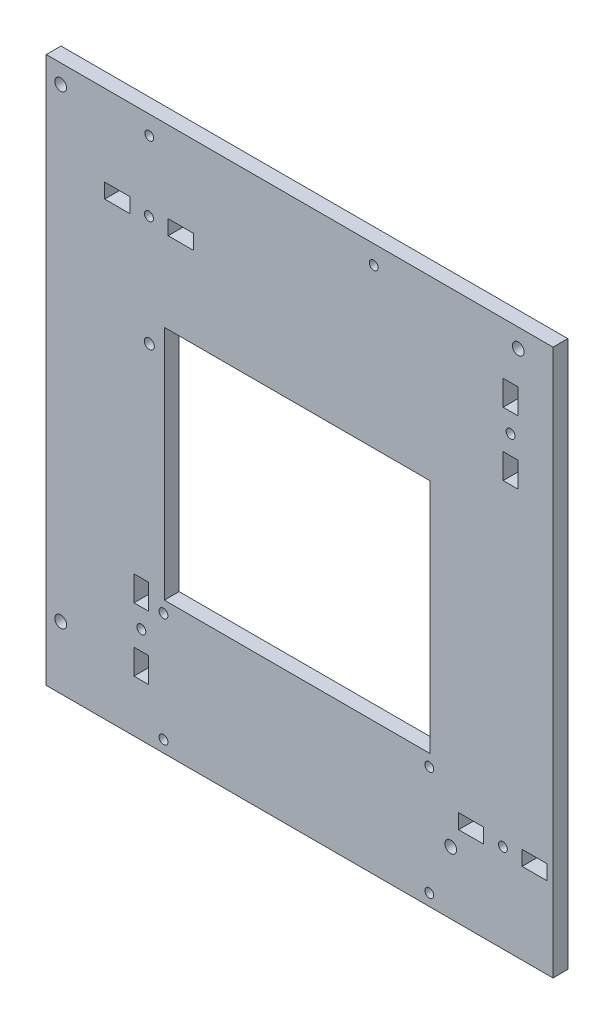
SolidWorks part; units mm, degrees
ref_plane "Front Plane" through (0, 0, 0) normal (0, 0, 1) x (1, 0, 0)
ref_plane "Top Plane" through (0, 0, 0) normal (0, 1, 0) x (1, 0, 0)
ref_plane "Right Plane" through (0, 0, 0) normal (1, 0, 0) x (0, 0, -1)
sketch "Sketch2" plane through (0, 0, 0) normal (0, 0, 1) x (1, 0, 0)
  line L0 (104.43, 85) -> (-85, -100) construction
  line L1 (-85, 85) -> (104.43, 85)
  line L2 (-85, 85) -> (-85, -100)
  line L3 (-85, -100) -> (104.43, -100)
  line L4 (104.43, 85) -> (104.43, -100)
  line L5 (96.43, 71.875) -> (96.43, 85) construction
  line L6 (88.43, -89.415) -> (87.11, -89.415) construction
  line L7 (96.43, -86.875) -> (96.43, -100) construction
  line L8 (88.43, 73.415) -> (88.43, -88.415) construction
  line L9 (87.11, -89.415) -> (87.11, 73.415) construction
  line L10 (88.43, 74.415) -> (87.11, 74.415) construction
  line L11 (-80.1, 78.65) -> (51.98, 78.65) construction
  line L12 (-80.1, 78.65) -> (-80.1, -78.83) construction
  line L13 (-80.1, -78.83) -> (51.98, -78.83) construction
  line L14 (51.98, 78.65) -> (51.98, -78.83) construction
  line L15 (74.84, 78.65) -> (-80.1, 78.65) construction
  line L16 (74.84, 78.65) -> (74.84, -78.83) construction
  line L17 (74.84, -78.83) -> (-80.1, -78.83) construction
  line L18 (-80.1, 78.65) -> (-80.1, -78.83) construction
  line L19 (88.93, -89.915) -> (86.61, -89.915)
  line L20 (88.93, -89.915) -> (88.93, 74.915)
  line L21 (88.93, 74.915) -> (86.61, 74.915)
  line L22 (86.61, -89.915) -> (86.61, 74.915)
  line L23 (88.93, -89.915) -> (86.61, 74.915) construction
  line L24 (88.93, 74.915) -> (86.61, -89.915) construction
  line L25 (-56.7109, 57.5) -> (-65.2109, 57.5)
  line L26 (25.9, 78.65) -> (-50.1, 78.65) construction
  line L27 (45, -55) -> (-45, -55)
  line L28 (45, -55) -> (45, 25)
  line L29 (45, 25) -> (-45, 25)
  line L30 (-45, -55) -> (-45, 25)
  line L31 (45, -55) -> (-45, 25) construction
  line L32 (45, 25) -> (-45, -55) construction
  line L33 (25.9, 78.65) -> (25.9, 17.65) construction
  line L34 (25.9, 17.65) -> (-50.1, 17.65) construction
  line L35 (-50.1, 78.65) -> (-50.1, 17.65) construction
  line L36 (-35.2109, 52.5) -> (-43.7109, 52.5)
  line L37 (-35.2109, 52.5) -> (-35.2109, 57.5)
  line L38 (-35.2109, 57.5) -> (-43.7109, 57.5)
  line L39 (-65.2109, 52.5) -> (-65.2109, 57.5)
  line L40 (-43.7109, 55) -> (-56.7109, 55) construction
  line L41 (-43.7109, 52.5) -> (-43.7109, 57.5)
  line L42 (74.715, 58.9259) -> (74.715, 67.4259)
  line L43 (-56.7109, 52.5) -> (-56.7109, 57.5)
  line L44 (-56.7109, 52.5) -> (-65.2109, 52.5)
  line L45 (69.715, 37.4259) -> (69.715, 45.9259)
  line L46 (69.715, 37.4259) -> (74.715, 37.4259)
  line L47 (74.715, 37.4259) -> (74.715, 45.9259)
  line L48 (69.715, 67.4259) -> (74.715, 67.4259)
  line L49 (69.715, 45.9259) -> (74.715, 45.9259)
  line L50 (69.715, 58.9259) -> (74.715, 58.9259)
  line L51 (69.715, 58.9259) -> (69.715, 67.4259)
  line L52 (72.215, 45.9259) -> (72.215, 58.9259) construction
  line L53 (76.1409, -72.5) -> (84.6409, -72.5)
  line L54 (54.6409, -67.5) -> (63.1409, -67.5)
  line L55 (54.6409, -67.5) -> (54.6409, -72.5)
  line L56 (54.6409, -72.5) -> (63.1409, -72.5)
  line L57 (84.6409, -67.5) -> (84.6409, -72.5)
  line L58 (63.1409, -67.5) -> (63.1409, -72.5)
  line L59 (76.1409, -67.5) -> (76.1409, -72.5)
  line L60 (76.1409, -67.5) -> (84.6409, -67.5)
  line L61 (63.1409, -70) -> (76.1409, -70) construction
  line L62 (-55.285, -73.9259) -> (-55.285, -82.4259)
  line L63 (-50.285, -52.4259) -> (-50.285, -60.9259)
  line L64 (-50.285, -52.4259) -> (-55.285, -52.4259)
  line L65 (-55.285, -52.4259) -> (-55.285, -60.9259)
  line L66 (-50.285, -82.4259) -> (-55.285, -82.4259)
  line L67 (-50.285, -60.9259) -> (-55.285, -60.9259)
  line L68 (-50.285, -73.9259) -> (-55.285, -73.9259)
  line L69 (-50.285, -73.9259) -> (-50.285, -82.4259)
  line L70 (-52.785, -60.9259) -> (-52.785, -73.9259) construction
  line L71 (74.715, 67.4259) -> (69.715, 67.4259) construction
  line L72 (69.715, 67.4259) -> (69.715, 58.9259) construction
  circle A0 centre (-80.1, 78.65) radius 1.98
  circle A1 centre (74.84, 78.65) radius 1.98
  circle A2 centre (51.98, -78.83) radius 1.98
  circle A3 centre (-80.1, -78.83) radius 1.98
  circle A4 centre (25.9, 78.65) radius 1.5
  circle A5 centre (-50.1, 78.65) radius 1.5
  circle A6 centre (-50.1, 17.65) radius 1.6948
  circle A7 centre (-50.2109, 55) radius 1.5
  circle A8 centre (72.215, 52.4259) radius 1.5
  circle A9 centre (69.6409, -70) radius 1.5
  circle A10 centre (-52.785, -67.4259) radius 1.5
  circle A11 centre (9.715, -7.5) radius 132.3903 construction
  point P8 (0, -15)
  point P28 (87.77, -7.5)
  dimension "D8" = 3
  dimension "D1" = 0.5
  dimension "D2" = 0.5
  dimension "D3" = 0.5
  dimension "D4" = 0.5
  dimension "D5" = 76
  dimension "D6" = 61
  dimension "D7" = 30
  dimension "D9" = 4
extrude "Boss-Extrude1" add sketch "Sketch2" along normal blind 5
sketch "Sketch3" plane through (0, 0, 5) normal (0, 0, 1) x (-1, 0, 0)
  line L1 (-44.715, 96) -> (45.285, 96) construction
  line L2 (-44.715, 96) -> (-44.715, 59) construction
  line L3 (-44.715, 59) -> (45.285, 59) construction
  line L4 (45.285, 96) -> (45.285, 59) construction
  line L5 (50.285, 82.4259) -> (50.285, 73.9259) construction
  line L6 (0, 55) -> (0, 100) construction
  line L7 (45, 55) -> (-45, 55) construction
  line L8 (85, 100) -> (-104.43, 100) construction
  line L9 (45.285, 77.5) -> (0, 77.5) construction
  circle A0 centre (45.285, 59) radius 1.5
  circle A1 centre (-44.715, 59) radius 1.5
  circle A2 centre (-44.715, 96) radius 1.5
  circle A3 centre (45.285, 96) radius 1.5
  dimension "D3" = 3
  dimension "D1" = 90
  dimension "D2" = 37
  dimension "D4" = 5
extrude "Cut-Extrude1" cut sketch "Sketch3" against normal blind 10
sketch "Sketch4" plane through (0, 0, 5) normal (0, 0, 1) x (1, 0, 0)
  line L0 (86.61, 85) -> (86.61, -124.4264)
  line L1 (104.43, 85) -> (-85, 85) construction
  line L2 (86.61, 74.915) -> (86.61, -89.915) construction
extrude "Cut-Extrude2" cut sketch "Sketch4" against normal through all and the other way through all
